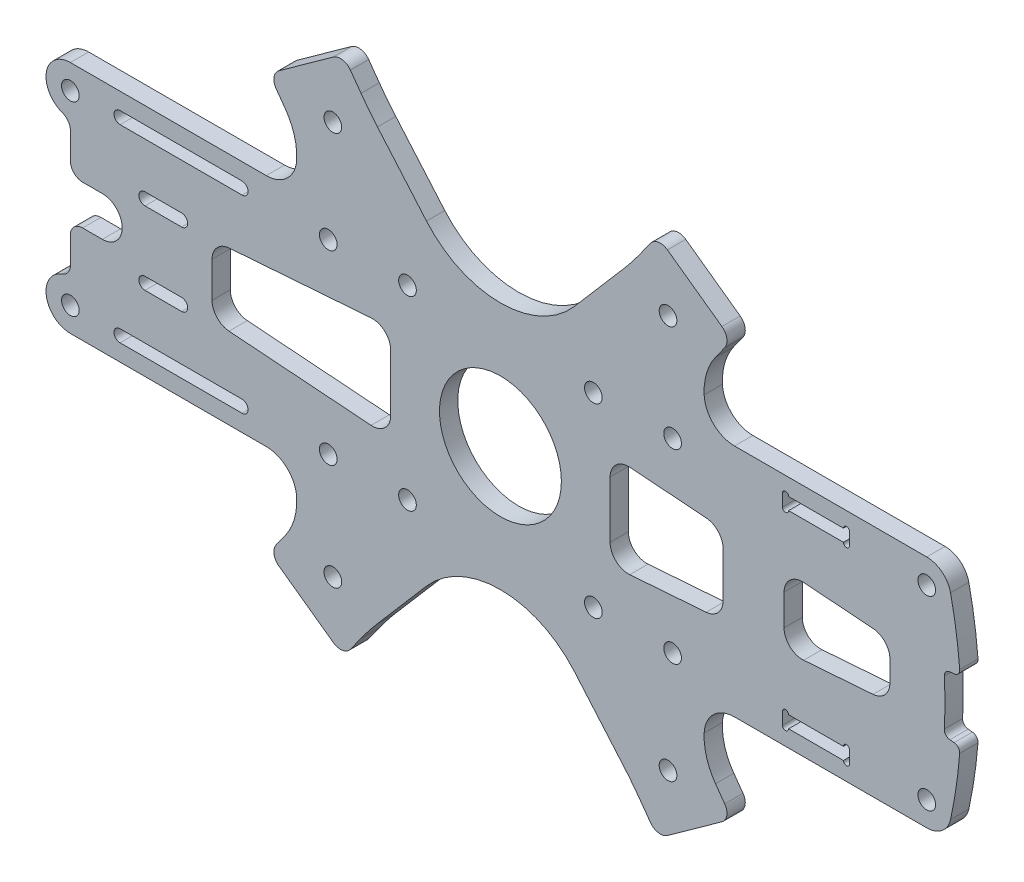
SolidWorks part; units mm, degrees
material "Thornel Mat VMA"
ref_plane "Front Plane" through (0, 0, 0) normal (0, 0, 1) x (1, 0, 0)
ref_plane "Top Plane" through (0, 0, 0) normal (0, 1, 0) x (1, 0, 0)
ref_plane "Right Plane" through (0, 0, 0) normal (1, 0, 0) x (0, 0, -1)
sketch "Sketch1" plane through (0, 0, 0) normal (0, 0, 1) x (1, 0, 0)
  line L0 (57.2807, -14.5) -> (57.2807, -16.5)
  line L1 (56.2807, -16.5) -> (47.2807, -16.5)
  line L2 (46.2807, -16.5) -> (46.2807, -14.5)
  line L3 (47.2807, -14.5) -> (56.2807, -14.5)
  line L4 (61.1287, 4.6848) -> (49.7552, 5.5246)
  line L5 (46.5343, 2.5327) -> (46.5343, -2.5327)
  line L6 (49.7552, -5.5246) -> (61.1287, -4.6848)
  line L7 (-47.316, 2.918) -> (-47.316, -2.918)
  line L8 (-44.5369, -5.9099) -> (-21.2209, -7.6314)
  line L9 (-18, -4.6395) -> (-18, 4.6395)
  line L10 (-21.2209, 7.6314) -> (-44.5369, 5.9099)
  line L11 (21.2209, 7.6314) -> (33.7552, 6.7059)
  line L12 (36.5343, 3.7141) -> (36.5343, -3.7141)
  line L13 (33.7552, -6.7059) -> (21.2209, -7.6314)
  line L14 (18, -4.6395) -> (18, 4.6395)
  line L15 (57.2807, 14.5) -> (57.2807, 16.5)
  line L16 (56.2807, 16.5) -> (47.2807, 16.5)
  line L17 (46.2807, 16.5) -> (46.2807, 14.5)
  line L18 (47.2807, 14.5) -> (56.2807, 14.5)
  line L19 (-58.316, 7) -> (-52.316, 7)
  line L20 (-52.316, 5) -> (-58.316, 5)
  line L21 (-58.316, -7) -> (-52.316, -7)
  line L22 (-52.316, -5) -> (-58.316, -5)
  line L23 (24.6144, -41.15) -> (22.8708, -38.7216)
  line L24 (20.1745, -35.2929) -> (12.1337, -25.9382)
  line L25 (-12.1337, -25.9382) -> (-20.1745, -35.2929)
  line L26 (-22.8708, -38.7216) -> (-24.6144, -41.15)
  line L27 (-27.4055, -41.608) -> (-36.3406, -35.1921)
  line L28 (-36.7986, -32.401) -> (-35.2934, -30.3048)
  line L29 (-38.4212, -19.25) -> (-70.5603, -19.25)
  line L30 (-70.5603, -9.5931) -> (-70.5603, -5.25)
  line L31 (-68.5603, -3.25) -> (-65.3092, -3.25)
  line L32 (-65.3092, 3.25) -> (-68.5603, 3.25)
  line L33 (-70.5603, 5.25) -> (-70.5603, 9.5931)
  line L34 (-70.5603, 19.25) -> (-38.4212, 19.25)
  line L35 (-35.2934, 30.3048) -> (-36.7986, 32.401)
  line L36 (-36.3406, 35.1921) -> (-27.4055, 41.608)
  line L37 (-24.6144, 41.15) -> (-22.8708, 38.7216)
  line L38 (-20.1745, 35.2929) -> (-12.1337, 25.9382)
  line L39 (12.1337, 25.9382) -> (20.1745, 35.2929)
  line L40 (22.8708, 38.7216) -> (24.6144, 41.15)
  line L41 (27.4055, 41.608) -> (36.3406, 35.1921)
  line L42 (36.7986, 32.401) -> (35.2934, 30.3048)
  line L43 (38.4212, 19.25) -> (69.9498, 19.25)
  line L44 (74.4479, 4.8846) -> (73.745, 4.8231)
  line L45 (73.745, -4.8231) -> (74.4479, -4.8846)
  line L46 (69.9498, -19.25) -> (38.4212, -19.25)
  line L47 (35.2934, -30.3048) -> (36.7986, -32.401)
  line L48 (36.3406, -35.1921) -> (27.4055, -41.608)
  line L49 (-42.4052, -14.5) -> (-62.4052, -14.5)
  line L50 (-62.4052, -16.5) -> (-42.4052, -16.5)
  line L51 (-42.4052, 14.5) -> (-62.4052, 14.5)
  line L52 (-62.4052, 16.5) -> (-42.4052, 16.5)
  circle A3 centre (0, 0) radius 10
  arc A21 (57.2807, -14.5) -> (56.2807, -14.5) centre (56.7807, -14.5) ccw
  arc A22 (56.2807, -16.5) -> (57.2807, -16.5) centre (56.7807, -16.5) ccw
  arc A23 (46.2807, -16.5) -> (47.2807, -16.5) centre (46.7807, -16.5) ccw
  arc A24 (47.2807, -14.5) -> (46.2807, -14.5) centre (46.7807, -14.5) ccw
  arc A25 (49.7552, 5.5246) -> (46.5343, 2.5327) centre (49.5343, 2.5327) ccw
  arc A26 (46.5343, -2.5327) -> (49.7552, -5.5246) centre (49.5343, -2.5327) ccw
  arc A27 (61.1287, -4.6848) -> (63.9066, -1.7763) centre (60.9078, -1.693) ccw
  arc A28 (63.9066, -1.7763) -> (63.9066, 1.7763) centre (0, 0) ccw
  arc A29 (63.9066, 1.7763) -> (61.1287, 4.6848) centre (60.9078, 1.693) ccw
  arc A30 (-44.5369, 5.9099) -> (-47.316, 2.918) centre (-44.316, 2.918) ccw
  arc A31 (-47.316, -2.918) -> (-44.5369, -5.9099) centre (-44.316, -2.918) ccw
  arc A32 (-21.2209, -7.6314) -> (-18, -4.6395) centre (-21, -4.6395) ccw
  arc A33 (-18, 4.6395) -> (-21.2209, 7.6314) centre (-21, 4.6395) ccw
  arc A34 (21.2209, 7.6314) -> (18, 4.6395) centre (21, 4.6395) ccw
  arc A35 (36.5343, 3.7141) -> (33.7552, 6.7059) centre (33.5343, 3.7141) ccw
  arc A36 (33.7552, -6.7059) -> (36.5343, -3.7141) centre (33.5343, -3.7141) ccw
  arc A37 (18, -4.6395) -> (21.2209, -7.6314) centre (21, -4.6395) ccw
  arc A38 (56.2807, 14.5) -> (57.2807, 14.5) centre (56.7807, 14.5) ccw
  arc A39 (57.2807, 16.5) -> (56.2807, 16.5) centre (56.7807, 16.5) ccw
  arc A40 (47.2807, 16.5) -> (46.2807, 16.5) centre (46.7807, 16.5) ccw
  arc A41 (46.2807, 14.5) -> (47.2807, 14.5) centre (46.7807, 14.5) ccw
  arc A42 (-58.316, 7) -> (-59.316, 6) centre (-58.316, 6) ccw
  arc A43 (-52.316, 5) -> (-52.316, 7) centre (-52.316, 6) ccw
  arc A44 (-59.316, 6) -> (-58.316, 5) centre (-58.316, 6) ccw
  arc A45 (-59.316, -6) -> (-58.316, -7) centre (-58.316, -6) ccw
  arc A46 (-52.316, -7) -> (-52.316, -5) centre (-52.316, -6) ccw
  arc A47 (-58.316, -5) -> (-59.316, -6) centre (-58.316, -6) ccw
  arc A48 (24.6144, -41.15) -> (27.4055, -41.608) centre (26.239, -39.9834) ccw
  arc A49 (22.8708, -38.7216) -> (20.1745, -35.2929) centre (-17.7433, -67.8849) ccw
  arc A50 (12.1337, -25.9382) -> (-12.1337, -25.9382) centre (0, -36.3676) ccw
  arc A51 (-20.1745, -35.2929) -> (-22.8708, -38.7216) centre (17.7433, -67.8849) ccw
  arc A52 (-27.4055, -41.608) -> (-24.6144, -41.15) centre (-26.239, -39.9834) ccw
  arc A53 (-36.7986, -32.401) -> (-36.3406, -35.1921) centre (-35.1741, -33.5675) ccw
  arc A54 (-35.2934, -30.3048) -> (-33.4261, -24.0279) centre (-43.4163, -24.4721) ccw
  arc A55 (-33.4261, -24.0279) -> (-38.4212, -19.25) centre (-38.4212, -24.25) ccw
  arc A56 (-71.8937, -11.4788) -> (-70.5603, -19.25) centre (-70.5603, -15.25) ccw
  arc A57 (-71.8937, -11.4788) -> (-70.5603, -9.5931) centre (-72.5603, -9.5931) ccw
  arc A58 (-68.5603, -3.25) -> (-70.5603, -5.25) centre (-68.5603, -5.25) ccw
  arc A59 (-65.3092, -3.25) -> (-65.3092, 3.25) centre (-65.3092, 0) ccw
  arc A60 (-70.5603, 5.25) -> (-68.5603, 3.25) centre (-68.5603, 5.25) ccw
  arc A61 (-70.5603, 9.5931) -> (-71.8937, 11.4788) centre (-72.5603, 9.5931) ccw
  arc A62 (-70.5603, 19.25) -> (-71.8937, 11.4788) centre (-70.5603, 15.25) ccw
  arc A63 (-38.4212, 19.25) -> (-33.4261, 24.0279) centre (-38.4212, 24.25) ccw
  arc A64 (-33.4261, 24.0279) -> (-35.2934, 30.3048) centre (-43.4163, 24.4721) ccw
  arc A65 (-36.3406, 35.1921) -> (-36.7986, 32.401) centre (-35.1741, 33.5675) ccw
  arc A66 (-24.6144, 41.15) -> (-27.4055, 41.608) centre (-26.239, 39.9834) ccw
  arc A67 (-22.8708, 38.7216) -> (-20.1745, 35.2929) centre (17.7433, 67.8849) ccw
  arc A68 (-12.1337, 25.9382) -> (12.1337, 25.9382) centre (0, 36.3676) ccw
  arc A69 (20.1745, 35.2929) -> (22.8708, 38.7216) centre (-17.7433, 67.8849) ccw
  arc A70 (27.4055, 41.608) -> (24.6144, 41.15) centre (26.239, 39.9834) ccw
  arc A71 (36.7986, 32.401) -> (36.3406, 35.1921) centre (35.1741, 33.5675) ccw
  arc A72 (35.2934, 30.3048) -> (33.4261, 24.0279) centre (43.4163, 24.4721) ccw
  arc A73 (33.4261, 24.0279) -> (38.4212, 19.25) centre (38.4212, 24.25) ccw
  arc A74 (73.858, 16.102) -> (69.9498, 19.25) centre (69.9498, 15.25) ccw
  arc A75 (75.3576, 5.9597) -> (73.858, 16.102) centre (0, 0) ccw
  arc A76 (74.4479, 4.8846) -> (75.3576, 5.9597) centre (74.3607, 5.8808) ccw
  arc A77 (73.745, 4.8231) -> (72.8335, 3.7752) centre (73.8322, 3.8269) ccw
  arc A78 (72.8335, -3.7752) -> (72.8335, 3.7752) centre (0, 0) ccw
  arc A79 (72.8335, -3.7752) -> (73.745, -4.8231) centre (73.8322, -3.8269) ccw
  arc A80 (75.3576, -5.9597) -> (74.4479, -4.8846) centre (74.3607, -5.8808) ccw
  arc A81 (73.858, -16.102) -> (75.3576, -5.9597) centre (0, 0) ccw
  arc A82 (69.9498, -19.25) -> (73.858, -16.102) centre (69.9498, -15.25) ccw
  arc A83 (38.4212, -19.25) -> (33.4261, -24.0279) centre (38.4212, -24.25) ccw
  arc A84 (33.4261, -24.0279) -> (35.2934, -30.3048) centre (43.4163, -24.4721) ccw
  arc A85 (36.3406, -35.1921) -> (36.7986, -32.401) centre (35.1741, -33.5675) ccw
  arc A86 (-42.4052, -16.5) -> (-42.4052, -14.5) centre (-42.4052, -15.5) ccw
  arc A87 (-62.4052, -14.5) -> (-62.4052, -16.5) centre (-62.4052, -15.5) ccw
  arc A88 (-42.4052, 14.5) -> (-42.4052, 16.5) centre (-42.4052, 15.5) ccw
  arc A89 (-62.4052, 16.5) -> (-62.4052, 14.5) centre (-62.4052, 15.5) ccw
  dimension "D1" = 20
extrude "Boss-Extrude1" add sketch "Sketch1" along normal blind 3
hole_wizard "M2.5 Clearance Hole1" positions "Sketch4" profile "Sketch5" hole size "M2.5" standard "ANSI Metric" end condition up to next
sketch "Sketch4" plane through (0, 0, 3) normal (0, 0, 1) x (1, 0, 0)
  line L0 (-70.5603, 15.25) -> (69.9498, 15.25) construction
  line L2 (-27.4986, 32.3079) -> (-15.25, 15.25) construction
  line L4 (15.25, 15.25) -> (27.4986, 32.3079) construction
  line L7 (0, 0) -> (50000, 0) construction
  line L8 (15.25, -15.25) -> (27.4986, -32.3079) construction
  line L9 (-27.4986, -32.3079) -> (-15.25, -15.25) construction
  line L10 (-70.5603, -15.25) -> (69.9498, -15.25) construction
  arc A0 (73.858, 16.102) -> (69.9498, 19.25) centre (69.9498, 15.25) ccw construction
  arc A1 (-70.5603, 19.25) -> (-71.8937, 11.4788) centre (-70.5603, 15.25) ccw construction
  point P2 (-70.5603, 15.25)
  point P5 (-28.25, 15.25)
  point P8 (-15.25, 15.25)
  point P11 (15.25, 15.25)
  point P14 (28.25, 15.25)
  point P17 (69.9498, 15.25)
  point P42 (27.4986, 32.3079)
  point P45 (-27.4986, 32.3079)
  point P156 (15.25, -15.25)
  point P157 (27.4986, -32.3079)
  point P158 (-27.4986, -32.3079)
  point P159 (-15.25, -15.25)
  point P160 (-70.5603, -15.25)
  point P161 (69.9498, -15.25)
  point P162 (28.25, -15.25)
  point P163 (-28.25, -15.25)
  dimension "D1" = 42.3103
  dimension "D2" = 13
  dimension "D3" = 30.5
  dimension "D4" = 13
  dimension "D5" = 54.319
  dimension "D6" = 21
  dimension "D7" = 54.319
sketch "Sketch5" plane through (-70.5603, 15.25, 3) normal (1, 0, 0) x (0, -1, 0)
  line L0 (0, 0) -> (0, 3)
  line L1 (0, 3) -> (1.45, 3)
  line L2 (1.45, 3) -> (1.45, 0)
  line L5 (1.45, 0) -> (0, 0)
  line L11 (0, -6.35) -> (0, 107.95) construction
  dimension "Thru Hole Dia." = 2.9
  dimension "Thru Hole Depth" = 3
